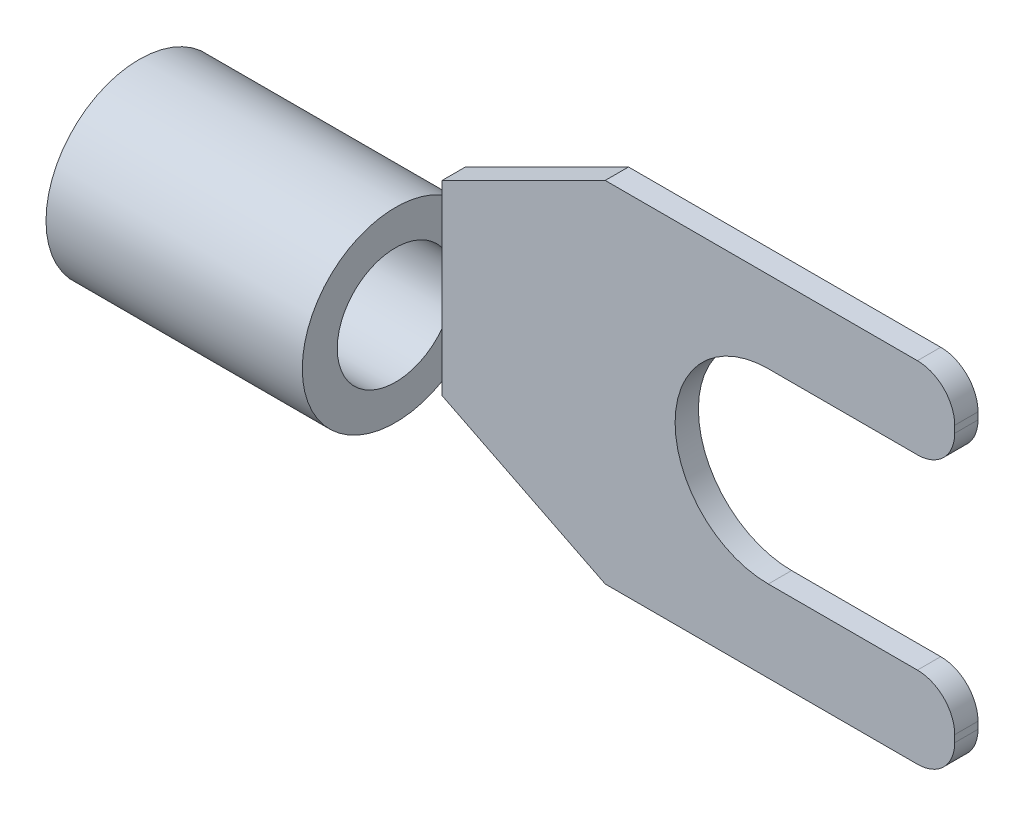
SolidWorks part; units mm, degrees
ref_plane "前视基准面" through (0, 0, 0) normal (0, 0, 1) x (1, 0, 0)
ref_plane "上视基准面" through (0, 0, 0) normal (0, 1, 0) x (1, 0, 0)
ref_plane "右视基准面" through (0, 0, 0) normal (1, 0, 0) x (0, 0, -1)
sketch "草图1" plane through (0, 0, 0) normal (0, 0, 1) x (1, 0, 0)
  line L0 (-59.949, 0) -> (64.78, 0) construction
  line L1 (0, 2) -> (3.2, 2)
  line L2 (-3.5, 3.75) -> (3.2, 3.75)
  line L3 (-34.038, 2.875) -> (50.8649, 2.875) construction
  line L4 (4, -2.95) -> (4, -2.8)
  line L5 (-3.5, -3.75) -> (3.2, -3.75)
  line L6 (0, -2) -> (3.2, -2)
  line L7 (4, 2.95) -> (4, 2.8)
  line L8 (0, -5.9925) -> (0, 5.2415) construction
  line L9 (-3.5, 3.75) -> (-7, 2)
  line L10 (-7, 2) -> (-12.5, 2)
  line L11 (-7, -2) -> (-12.5, -2)
  line L12 (-3.5, -3.75) -> (-7, -2)
  line L13 (-12.5, 2) -> (-12.5, -2)
  arc A0 (4, 2.8) -> (3.2, 2) centre (3.2, 2.8) cw
  arc A1 (4, 2.95) -> (3.2, 3.75) centre (3.2, 2.95) ccw
  arc A2 (4, -2.95) -> (3.2, -3.75) centre (3.2, -2.95) cw
  arc A3 (4, -2.8) -> (3.2, -2) centre (3.2, -2.8) ccw
  arc A4 (0, 2) -> (0, -2) centre (0, 0) ccw
  dimension "D1" = 0.8
  dimension "D5" = 4
  dimension "D2" = 7.5
  dimension "D3" = 4
  dimension "D4" = 7.5
  dimension "D6" = 4
  dimension "D7" = 5.5
  dimension "D8" = 16.5
extrude "凸台-拉伸1" add sketch "草图1" along normal blind 0.5
sketch "草图2" plane through (-12.5, 0, 0) normal (-1, 0, 0) x (0, 0, 1)
  line L0 (-1.5803, 0) -> (2.5411, 0) construction
  line L1 (0, 2) -> (0, -2) construction
  circle A0 centre (1.5, 0) radius 1.25
  circle A1 centre (1.5, 0) radius 2
  dimension "D1" = 4
  dimension "D2" = 1.5
  dimension "D3" = 2.5
extrude "凸台-拉伸2" add sketch "草图2" against normal up to vertex (5.5 mm away) up to point (-7, -2, 0.5)
sketch "草图3" plane through (-12.5, 0, 0) normal (-1, 0, 0) x (0, 0, 1)
  circle A0 centre (1.5, 0) radius 1.25
  arc A1 (0.5, -0.75) -> (0.5, 0.75) centre (1.5, 0) ccw construction
extrude "切除-拉伸1" cut sketch "草图3" against normal up to surface (5.5 mm away) up to face at (-7, 0, 1.8125)
sketch "草图4" plane through (-12.5, 0, 0) normal (-1, 0, 0) x (0, 0, 1)
  circle A0 centre (1.5, 0) radius 2
  arc A1 (0.5, -1.7321) -> (0.5, 1.7321) centre (1.5, 0) ccw construction
  circle A2 centre (1.5, 0) radius 4
  dimension "D1" = 2
extrude "切除-拉伸2" cut sketch "草图4" against normal up to surface (5.5 mm away) up to face at (-7, 0, 1.8125)
